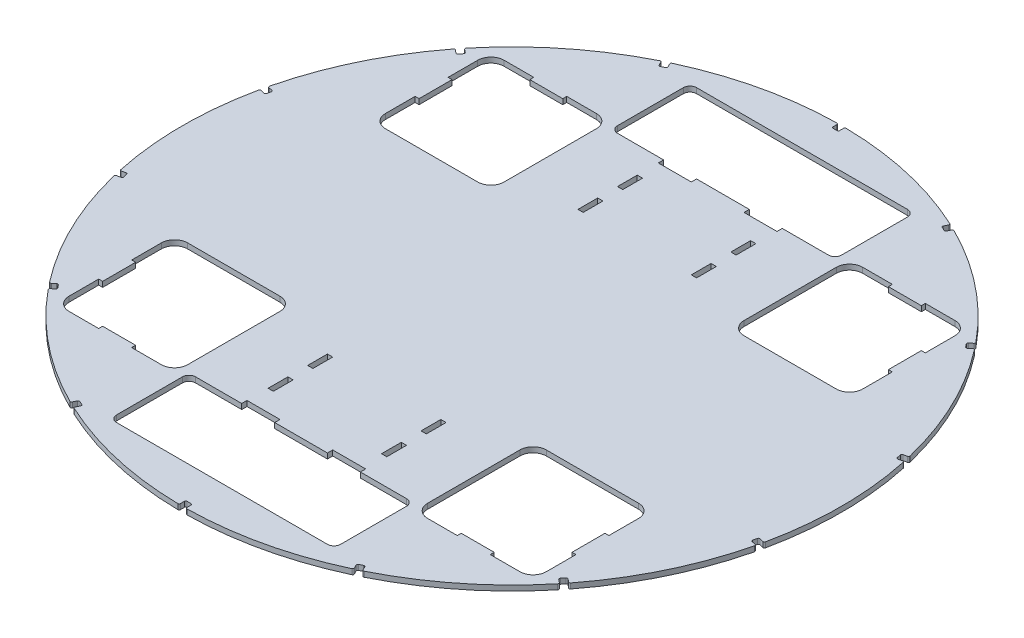
SolidWorks part; units mm, degrees
ref_plane "Front Plane" through (0, 0, 0) normal (0, 0, 1) x (1, 0, 0)
ref_plane "Top Plane" through (0, 0, 0) normal (0, 1, 0) x (1, 0, 0)
ref_plane "Right Plane" through (0, 0, 0) normal (1, 0, 0) x (0, 0, -1)
sketch "Sketch1" plane through (0, 0, 0) normal (0, 1, 0) x (1, 0, 0)
  circle A0 centre (0, 0) radius 250
extrude "Boss-Extrude1" add sketch "Sketch1" along normal blind 4
sketch "Sketch2" plane through (0, 4, 0) normal (0, 1, 0) x (1, 0, 0)
  line L0 (0, -250) -> (0, 250) construction
  line L1 (80, 220) -> (-80, 220)
  line L2 (85, 215) -> (85, 165)
  line L3 (80, 160) -> (-80, 160)
  line L4 (-85, 215) -> (-85, 165)
  line L5 (85, 220) -> (-85, 160) construction
  line L6 (85, 160) -> (-85, 220) construction
  line L7 (-55, 0) -> (55, 0) construction
  line L8 (85, -215) -> (85, -165)
  line L9 (80, -160) -> (-80, -160)
  line L10 (-85, -215) -> (-85, -165)
  line L11 (80, -220) -> (-80, -220)
  circle A0 centre (0, 0) radius 250 construction
  arc A1 (-80, 160) -> (-85, 165) centre (-80, 165) cw
  arc A2 (80, 160) -> (85, 165) centre (80, 165) ccw
  arc A3 (85, 215) -> (80, 220) centre (80, 215) ccw
  arc A4 (-80, 220) -> (-85, 215) centre (-80, 215) ccw
  arc A5 (-85, -215) -> (-80, -220) centre (-80, -215) ccw
  arc A6 (80, -220) -> (85, -215) centre (80, -215) ccw
  arc A7 (85, -165) -> (80, -160) centre (80, -165) ccw
  arc A8 (-80, -160) -> (-85, -165) centre (-80, -165) ccw
  point P0 (0, 190)
  point P5 (0, 0)
  point P11 (0, 0)
  point P33 (-85, -220)
  point P36 (85, -220)
  point P39 (85, -160)
  point P42 (-85, -160)
  dimension "D4" = 5
  dimension "D5" = 5
  dimension "D1" = 170
  dimension "D2" = 190
  dimension "D3" = 60
extrude "Cut-Extrude1" cut sketch "Sketch2" against normal blind 10
sketch "Sketch3" plane through (0, 4, 0) normal (0, 1, 0) x (1, 0, 0)
  line L0 (45, 160) -> (-45, 160)
  line L1 (-80, 160) -> (80, 160) construction
  line L2 (0, -2.2) -> (0, 2.2) construction
  line L3 (-45, 160) -> (-20, 160)
  line L4 (-45, 160) -> (-45, 156)
  line L5 (-45, 156) -> (-20, 156)
  line L6 (-20, 160) -> (-20, 156)
  line L7 (20, 160) -> (20, 156)
  line L8 (45, 156) -> (20, 156)
  line L9 (45, 160) -> (45, 156)
  line L10 (45, 160) -> (20, 160)
  line L11 (-2.2, 0) -> (2.2, 0) construction
  line L12 (45, -160) -> (20, -160)
  line L13 (45, -160) -> (45, -156)
  line L14 (45, -156) -> (20, -156)
  line L15 (20, -160) -> (20, -156)
  line L16 (-20, -160) -> (-20, -156)
  line L17 (-45, -156) -> (-20, -156)
  line L18 (-45, -160) -> (-45, -156)
  line L19 (-45, -160) -> (-20, -160)
  line L20 (45, -160) -> (-45, -160)
  point P5 (0, 160)
  point P24 (0, -160)
  line M7 (80, 160) -> (-80, 160)
  line M10 (-80, -160) -> (80, -160)
  dimension "D2" = 4
  dimension "D3" = 25
extrude "Cut-Extrude2" cut sketch "Sketch3" against normal blind 5 contours L6 L0 L4 L5 | L9 L7 L8 M7 | L18 L16 L17 M10 | L15 L13 L14 M10 region at (32.5, 4, -158) region at (-32.5, 4, -158) region at (-32.5, 4, 158) region at (32.5, 4, 158)
sketch "Sketch4" plane through (0, 4, 0) normal (0, 1, 0) x (1, 0, 0)
  line L0 (45, 160) -> (-45, 160)
  line L3 (80, 220) -> (-80, 220) construction
  line L4 (45, 160) -> (80, 160) construction
  line L5 (45, 140) -> (41, 140)
  line L6 (45, 140) -> (45, 125)
  line L7 (45, 125) -> (41, 125)
  line L8 (41, 140) -> (41, 125)
  line L9 (0, -2.2) -> (0, 2.2) construction
  line L10 (41, 110) -> (45, 110)
  line L11 (41, 110) -> (41, 95)
  line L12 (41, 95) -> (45, 95)
  line L13 (45, 110) -> (45, 95)
  line L14 (-45, 110) -> (-45, 95)
  line L15 (-41, 95) -> (-45, 95)
  line L16 (-41, 110) -> (-41, 95)
  line L17 (-41, 110) -> (-45, 110)
  line L18 (-41, 140) -> (-41, 125)
  line L19 (-45, 125) -> (-41, 125)
  line L20 (-45, 140) -> (-45, 125)
  line L21 (-45, 140) -> (-41, 140)
  line L22 (-2.2, 0) -> (2.2, 0) construction
  line L23 (-45, -140) -> (-41, -140)
  line L24 (-45, -140) -> (-45, -125)
  line L25 (-45, -125) -> (-41, -125)
  line L26 (-41, -140) -> (-41, -125)
  line L27 (-41, -110) -> (-45, -110)
  line L28 (-41, -110) -> (-41, -95)
  line L29 (-41, -95) -> (-45, -95)
  line L30 (-45, -110) -> (-45, -95)
  line L31 (45, -110) -> (45, -95)
  line L32 (41, -95) -> (45, -95)
  line L33 (41, -110) -> (41, -95)
  line L34 (41, -110) -> (45, -110)
  line L35 (41, -140) -> (41, -125)
  line L36 (45, -125) -> (41, -125)
  line L37 (45, -140) -> (45, -125)
  line L38 (45, -140) -> (41, -140)
  point P3 (0, 160)
  point P5 (0, 220)
  point P16 (45, 132.5)
  point P17 (45, 102.5)
  dimension "D1" = 0
  dimension "D2" = 4
  dimension "D3" = 0
  dimension "D4" = 90
  dimension "D5" = 15
  dimension "D6" = 20
  dimension "D7" = 15
  dimension "D8" = 4
  dimension "D9" = 30
extrude "Cut-Extrude3" cut sketch "Sketch4" against normal blind 20 contours L5 L8 L7 L6 | L13 L10 L11 L12 | L21 L20 L19 L18 | L16 L17 L14 L15 | L30 L27 L28 L29 | L23 L26 L25 L24 | L33 L34 L31 L32 | L38 L37 L36 L35 region at (43, 4, -132.5) region at (43, 4, -102.5) region at (-43, 4, -102.5) region at (-43, 4, -132.5) region at (-43, 4, 132.5) region at (-43, 4, 102.5) region at (43, 4, 102.5) region at (43, 4, 132.5)
sketch "Sketch7" plane through (0, 4, 0) normal (0, 1, 0) x (1, 0, 0)
  line L0 (0, -2.2) -> (0, 2.2) construction
  line L1 (-101, 75) -> (-171, 75)
  line L2 (-91, 85) -> (-91, 155)
  line L3 (-101, 165) -> (-171, 165)
  line L4 (-181, 85) -> (-181, 155)
  line L5 (-91, 75) -> (-181, 165) construction
  line L6 (-91, 165) -> (-181, 75) construction
  line L7 (91, 165) -> (181, 75) construction
  line L8 (91, 75) -> (181, 165) construction
  line L9 (181, 85) -> (181, 155)
  line L10 (101, 165) -> (171, 165)
  line L11 (91, 85) -> (91, 155)
  line L12 (101, 75) -> (171, 75)
  line L13 (-2.2, 0) -> (2.2, 0) construction
  line L14 (91, -75) -> (181, -165) construction
  line L15 (91, -165) -> (181, -75) construction
  line L16 (101, -75) -> (171, -75)
  line L17 (91, -85) -> (91, -155)
  line L18 (101, -165) -> (171, -165)
  line L19 (181, -85) -> (181, -155)
  line L20 (-91, -165) -> (-181, -75) construction
  line L21 (-91, -75) -> (-181, -165) construction
  line L22 (-181, -85) -> (-181, -155)
  line L23 (-101, -165) -> (-171, -165)
  line L24 (-91, -85) -> (-91, -155)
  line L25 (-101, -75) -> (-171, -75)
  arc A0 (-171, 165) -> (-181, 155) centre (-171, 155) ccw
  arc A1 (-91, 155) -> (-101, 165) centre (-101, 155) ccw
  arc A2 (-181, -155) -> (-171, -165) centre (-171, -155) ccw
  arc A3 (-101, -165) -> (-91, -155) centre (-101, -155) ccw
  arc A4 (-91, -85) -> (-101, -75) centre (-101, -85) ccw
  arc A5 (-171, -75) -> (-181, -85) centre (-171, -85) ccw
  arc A6 (91, -155) -> (101, -165) centre (101, -155) ccw
  arc A7 (171, -165) -> (181, -155) centre (171, -155) ccw
  arc A8 (181, -85) -> (171, -75) centre (171, -85) ccw
  arc A9 (101, -75) -> (91, -85) centre (101, -85) ccw
  arc A10 (101, 75) -> (91, 85) centre (101, 85) cw
  arc A11 (171, 75) -> (181, 85) centre (171, 85) ccw
  arc A12 (181, 155) -> (171, 165) centre (171, 155) ccw
  arc A13 (91, 155) -> (101, 165) centre (101, 155) cw
  arc A14 (-171, 75) -> (-181, 85) centre (-171, 85) cw
  arc A15 (-101, 75) -> (-91, 85) centre (-101, 85) ccw
  point P0 (-136, 120)
  point P12 (136, 120)
  point P19 (136, -120)
  point P24 (-136, -120)
  dimension "D5" = 10
  dimension "D6" = 10
  dimension "D7" = 10
  dimension "D1" = 90
  dimension "D2" = 90
  dimension "D3" = 136
  dimension "D4" = 120
extrude "Cut-Extrude4" cut sketch "Sketch7" against normal blind 5
sketch "Sketch8" plane through (0, 4, 0) normal (0, 1, 0) x (1, 0, 0)
  line L0 (-181, 155) -> (-181, 85) construction
  line L1 (-178, 107.5) -> (-184, 107.5)
  line L2 (-178, 107.5) -> (-178, 132.5)
  line L3 (-178, 132.5) -> (-184, 132.5)
  line L4 (-184, 107.5) -> (-184, 132.5)
  line L5 (-178, 107.5) -> (-184, 132.5) construction
  line L6 (-178, 132.5) -> (-184, 107.5) construction
  line L7 (-101, 165) -> (-171, 165) construction
  line L8 (-123.5, 162) -> (-148.5, 162)
  line L9 (-123.5, 162) -> (-123.5, 168)
  line L10 (-123.5, 168) -> (-148.5, 168)
  line L11 (-148.5, 162) -> (-148.5, 168)
  line L12 (-123.5, 162) -> (-148.5, 168) construction
  line L13 (-123.5, 168) -> (-148.5, 162) construction
  line L14 (0, -2.2) -> (0, 2.2) construction
  line L15 (123.5, 168) -> (148.5, 162) construction
  line L16 (123.5, 162) -> (148.5, 168) construction
  line L17 (178, 132.5) -> (184, 107.5) construction
  line L18 (178, 107.5) -> (184, 132.5) construction
  line L19 (148.5, 162) -> (148.5, 168)
  line L20 (123.5, 168) -> (148.5, 168)
  line L21 (123.5, 162) -> (123.5, 168)
  line L22 (123.5, 162) -> (148.5, 162)
  line L23 (184, 107.5) -> (184, 132.5)
  line L24 (178, 132.5) -> (184, 132.5)
  line L25 (178, 107.5) -> (178, 132.5)
  line L26 (178, 107.5) -> (184, 107.5)
  line L27 (-2.2, 0) -> (2.2, 0) construction
  line L28 (178, -107.5) -> (184, -132.5) construction
  line L29 (178, -132.5) -> (184, -107.5) construction
  line L30 (123.5, -162) -> (148.5, -168) construction
  line L31 (123.5, -168) -> (148.5, -162) construction
  line L32 (178, -107.5) -> (184, -107.5)
  line L33 (178, -107.5) -> (178, -132.5)
  line L34 (178, -132.5) -> (184, -132.5)
  line L35 (184, -107.5) -> (184, -132.5)
  line L36 (123.5, -162) -> (148.5, -162)
  line L37 (123.5, -162) -> (123.5, -168)
  line L38 (123.5, -168) -> (148.5, -168)
  line L39 (148.5, -162) -> (148.5, -168)
  line L40 (-123.5, -168) -> (-148.5, -162) construction
  line L41 (-123.5, -162) -> (-148.5, -168) construction
  line L42 (-178, -132.5) -> (-184, -107.5) construction
  line L43 (-178, -107.5) -> (-184, -132.5) construction
  line L44 (-148.5, -162) -> (-148.5, -168)
  line L45 (-123.5, -168) -> (-148.5, -168)
  line L46 (-123.5, -162) -> (-123.5, -168)
  line L47 (-123.5, -162) -> (-148.5, -162)
  line L48 (-184, -107.5) -> (-184, -132.5)
  line L49 (-178, -132.5) -> (-184, -132.5)
  line L50 (-178, -107.5) -> (-178, -132.5)
  line L51 (-178, -107.5) -> (-184, -107.5)
  point P0 (-181, 120)
  point P7 (-136, 165)
  point P24 (136, 165)
  point P25 (181, 120)
  point P36 (181, -120)
  point P37 (136, -165)
  point P46 (-136, -165)
  point P47 (-181, -120)
  dimension "D1" = 6
  dimension "D2" = 25
  dimension "D3" = 6
  dimension "D4" = 25
extrude "Boss-Extrude2" add sketch "Sketch8" against normal blind 4
sketch "Sketch11" plane through (0, 4, 0) normal (0, 1, 0) x (1, 0, 0)
  line L1 (1.5, 245) -> (-1.5, 245)
  line L2 (2.5, 246) -> (2.5, 255)
  line L3 (2.5, 255) -> (-2.5, 255)
  line L4 (-2.5, 246) -> (-2.5, 255)
  line L5 (2.5, 245) -> (-2.5, 255) construction
  line L6 (2.5, 255) -> (-2.5, 245) construction
  circle A0 centre (0, 0) radius 250 construction
  arc A1 (2.5, 246) -> (1.5, 245) centre (1.5, 246) cw
  arc A2 (-1.5, 245) -> (-2.5, 246) centre (-1.5, 246) cw
  point P0 (0, 250)
  dimension "D3" = 1
  dimension "D1" = 10
  dimension "D2" = 5
extrude "Cut-Extrude5" cut sketch "Sketch11" against normal blind 4
fillet "Fillet1" radius 1 2 edges at (2.5, 2, -249.9875) (-2.5, 2, -249.9875)
pattern_circular "CirPattern1" count 14 over 360 about axis through (0, 4, 0) along (0, -1, 0) of "Cut-Extrude5", "Fillet1"
